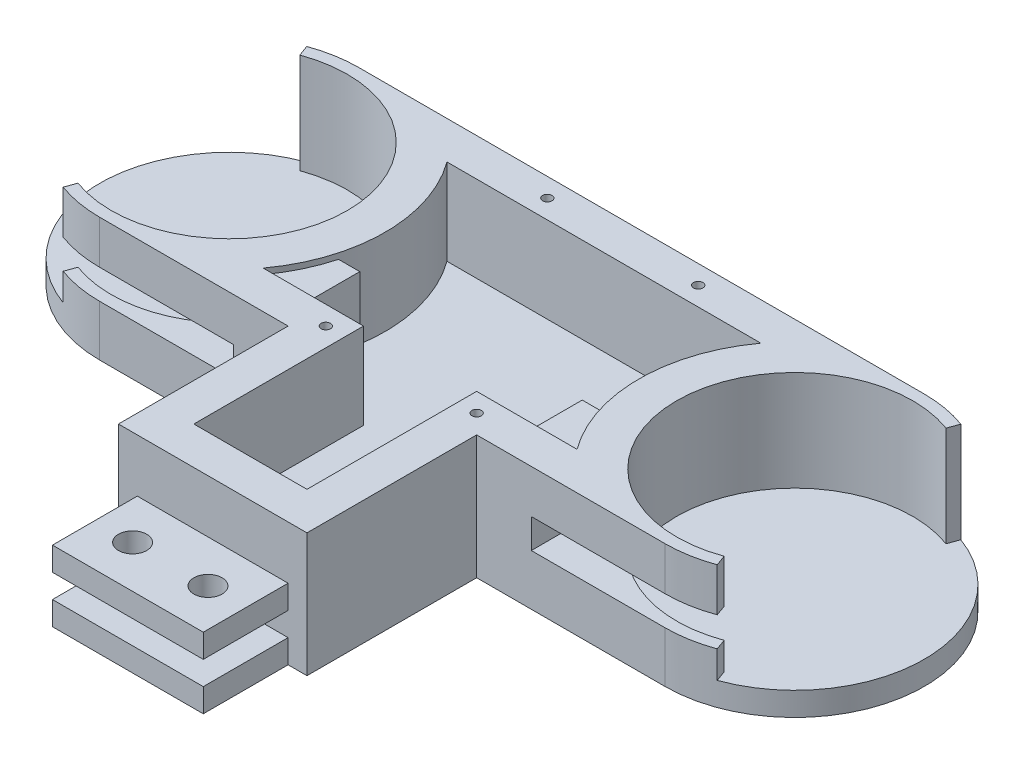
SolidWorks part; units mm, degrees
material "ABS PC"
ref_plane "Front Plane" through (0, 0, 0) normal (0, 0, 1) x (1, 0, 0)
ref_plane "Top Plane" through (0, 0, 0) normal (0, 1, 0) x (1, 0, 0)
ref_plane "Right Plane" through (0, 0, 0) normal (1, 0, 0) x (0, 0, -1)
sketch "Sketch1" plane through (0, 0, 0) normal (0, 1, 0) x (1, 0, 0)
  line L0 (-62.5313, 48.6245) -> (13.6438, 48.6245)
  line L1 (13.6438, 48.6245) -> (13.6438, -21.2255)
  line L2 (13.6438, -21.2255) -> (-62.5313, -21.2255)
  line L3 (-62.5313, 13.6995) -> (-74.4763, 46.5183)
  line L4 (-62.5313, 13.6995) -> (-74.4763, -19.1192)
  line L5 (-62.5313, 48.6245) -> (-62.5313, -21.2255)
  circle A0 centre (-62.5313, 13.6995) radius 34.925
  circle A1 centre (-62.5313, 13.6995) radius 31.8135
  dimension "D3" = 63.627
  dimension "D4" = 69.85
  dimension "D1" = 20
  dimension "D2" = 20
extrude "Boss-Extrude1" add sketch "Sketch1" along normal blind 26.9875 contours A1 L5 A0 | A1 L5 A0 L3 | A1 L4 A0 L5 | A0 L2 L1 L0 region at (-38.3878, 0, -37.843) region at (-11.352, 0, -13.6995) region at (-68.3006, 0, -46.4189) region at (-68.3006, 0, 19.0199)
extrude "Boss-Extrude5" add sketch "Sketch1<5>" against normal blind 6.35 contours A0 L2 L1 L0 | A0 region at (-11.352, 0, -13.6995)
sketch "Sketch1<5>" plane through (0, 0, 0) normal (0, 1, 0) x (1, 0, 0) same geometry as "Sketch1"
sketch "Sketch2" plane through (0, 26.9875, 0) normal (0, 1, 0) x (1, 0, 0)
  line L0 (-62.5313, 13.6995) -> (-53.4175, 13.6995)
  line L1 (-53.4175, 13.6995) -> (-53.4175, 3.6695)
  line L2 (13.6438, -21.2255) -> (-62.5313, -21.2255) construction
  line L3 (-53.4175, 3.6695) -> (-32.4413, 3.6695)
  line L4 (-53.4175, 3.6695) -> (-53.4175, 23.7295)
  line L5 (-53.4175, 23.7295) -> (-32.4413, 23.7295)
  line L6 (-32.4413, 3.6695) -> (-32.4413, 23.7295)
  line L7 (-53.4175, 3.6695) -> (-53.4175, -21.2255)
  line L8 (-53.4175, -21.2255) -> (13.6438, -21.2255)
  line L9 (13.6438, -21.2255) -> (13.6438, 48.6245)
  line L10 (13.6438, 48.6245) -> (-53.4175, 48.6245)
  line L11 (-62.5313, 48.6245) -> (13.6438, 48.6245) construction
  line L12 (-53.4175, 48.6245) -> (-53.4175, 23.7295)
  dimension "D1" = 9.1137
  dimension "D2" = 20.9763
  dimension "D3" = 20.06
  dimension "D4" = 10.03
mirror "Mirror1" about plane through (13.6438, 26.9875, 0) normal (1, 0, 0) of "Boss-Extrude1", "Boss-Extrude5"
sketch "Sketch3" plane through (0, 0, 21.2255) normal (0, 0, 1) x (1, 0, 0)
  line L0 (-53.4175, 26.9875) -> (13.6438, 26.9875) construction
  line L1 (-11.7562, 26.9875) -> (39.0438, 26.9875)
  line L2 (-11.7562, 26.9875) -> (-11.7562, -6.35)
  line L3 (-11.7562, -6.35) -> (39.0438, -6.35)
  line L4 (39.0438, 26.9875) -> (39.0438, -6.35)
  line L5 (89.8188, -6.35) -> (-62.5313, -6.35) construction
  line L8 (13.6438, 26.9875) -> (13.6438, -6.35)
  line L9 (89.8188, 26.9875) -> (-62.5313, 26.9875) construction
  line M5 (-62.5313, -6.35) -> (89.8188, -6.35)
  line M7 (89.8188, 26.9875) -> (-62.5313, 26.9875)
  dimension "D1" = 50.8
  dimension "D2" = 25.4
extrude "Boss-Extrude7" add sketch "Sketch3" along normal blind 45.72 contours L8 L1 L2 M5 | L8 L3 L4 M7 region at (0.9438, 10.3187, 21.2255) region at (26.3438, 10.3187, 21.2255)
sketch "Sketch6" plane through (0, 0, 66.9455) normal (0, 0, 1) x (1, 0, 0)
  line L0 (39.0438, 26.9875) -> (-11.7562, 26.9875) construction
  line L1 (4.7538, 26.9875) -> (22.5338, 26.9875)
  line L2 (4.7538, 26.9875) -> (4.7538, -6.35)
  line L3 (4.7538, -6.35) -> (22.5338, -6.35)
  line L4 (22.5338, 26.9875) -> (22.5338, -6.35)
  line L5 (-11.7562, -6.35) -> (39.0438, -6.35) construction
  line L6 (13.6438, 26.9875) -> (13.6438, -6.35)
  line M4 (-11.7562, -6.35) -> (39.0438, -6.35)
  line M6 (39.0438, 26.9875) -> (-11.7562, 26.9875)
  dimension "D1" = 17.78
  dimension "D2" = 8.89
extrude "Boss-Extrude8" add sketch "Sketch6" along normal blind 22.86 contours L6 L1 L2 M4 | L6 L3 L4 M6 region at (9.1988, 10.3188, 66.9455) region at (18.0888, 10.3187, 66.9455)
sketch "Sketch7" plane through (4.7538, 0, 0) normal (-1, 0, 0) x (0, 0, 1)
  line L0 (89.8055, 26.9875) -> (89.8055, -6.35) construction
  line L1 (66.9455, 26.9875) -> (89.8055, 26.9875)
  line L2 (66.9455, 26.9875) -> (66.9455, 12.446)
  line L3 (66.9455, 12.446) -> (89.8055, 12.446)
  line L4 (89.8055, 26.9875) -> (89.8055, 12.446)
  line L5 (66.9455, 26.9875) -> (66.9455, -6.35) construction
  line L6 (66.9455, 6.35) -> (89.8055, 6.35)
  line L7 (66.9455, 6.35) -> (66.9455, -0.254)
  line L8 (66.9455, -0.254) -> (89.8055, -0.254)
  line L9 (89.8055, 6.35) -> (89.8055, -0.254)
  line L10 (89.8055, -6.35) -> (66.9455, -6.35) construction
  dimension "D1" = 6.096
  dimension "D2" = 6.604
  dimension "D3" = 6.096
extrude "Cut-Extrude1" cut sketch "Sketch7" against normal blind 21.082
sketch "Sketch11" plane through (0, 0, 21.2255) normal (0, 0, 1) x (1, 0, 0)
  line L1 (-77.744, 15.3035) -> (-26.4882, 15.3035)
  line L2 (-77.744, 15.3035) -> (-77.744, 7.366)
  line L3 (-77.744, 7.366) -> (-26.4882, 7.366)
  line L4 (-26.4882, 15.3035) -> (-26.4882, 7.366)
  line L5 (-11.7562, 26.9875) -> (-62.5313, 26.9875) construction
  line L7 (-11.7562, -6.35) -> (-62.5313, -6.35) construction
  line L8 (-11.7562, 26.9875) -> (-11.7562, -6.35) construction
  dimension "D1" = 11.684
  dimension "D2" = 13.716
  dimension "D3" = 14.732
extrude "Cut-Extrude3" cut sketch "Sketch11" against normal blind 13.716
sketch "Sketch12" plane through (0, 26.9875, 0) normal (0, 1, 0) x (1, 0, 0)
  line L0 (13.6438, -66.9455) -> (13.6438, 48.6245)
  line L1 (39.0438, -66.9455) -> (-11.7562, -66.9455) construction
  line L2 (-62.5313, 48.6245) -> (89.8188, 48.6245) construction
ref_plane "Plane1" through (13.6438, 0, 0) normal (1, 0, 0) x (0, 0, -1)
mirror "Mirror2" about plane through (13.6438, 0, 0) normal (1, 0, 0) of "Cut-Extrude3"
shell "Shell1" thickness 10.16 removed face at (13.6438, 26.9875, 0.7467)
sketch "Sketch13" plane through (0, 26.9875, 0) normal (0, 1, 0) x (1, 0, 0)
  circle A0 centre (33.9638, -16.1455) radius 1.2687
  circle A1 centre (-6.6762, -16.1455) radius 1.2687
  circle A2 centre (-6.6762, 43.5445) radius 1.2687
  circle A3 centre (33.9638, 43.5445) radius 1.2687
  dimension "D1" = 2.5375
  dimension "D2" = 2.5375
  dimension "D3" = 2.5375
  dimension "D4" = 2.5375
extrude "Cut-Extrude4" cut sketch "Sketch13" against normal blind 35.56
sketch "Sketch14" plane through (0, 0, 66.9455) normal (0, 0, 1) x (1, 0, 0)
  line L0 (-11.7562, -6.35) -> (4.7538, -6.35) construction
  line L1 (-6.6762, 6.35) -> (33.9638, 6.35)
  line L2 (-6.6762, 6.35) -> (-6.6762, 12.7)
  line L3 (-6.6762, 12.7) -> (33.9638, 12.7)
  line L4 (33.9638, 6.35) -> (33.9638, 12.7)
  line L5 (-6.6762, -6.35) -> (33.9638, -6.35)
  line L6 (-6.6762, -6.35) -> (-6.6762, 0)
  line L7 (-6.6762, 0) -> (33.9638, 0)
  line L8 (33.9638, -6.35) -> (33.9638, 0)
  line L9 (13.6438, -18.3356) -> (13.6438, 18.3356) construction
  dimension "D1" = 20.32
  dimension "D2" = 20.32
  dimension "D3" = 6.35
  dimension "D4" = 6.35
  dimension "D5" = 20.32
  dimension "D6" = 20.32
  dimension "D7" = 6.35
extrude "Boss-Extrude9" add sketch "Sketch14" along normal up to surface (22.86 mm away) up to face at (13.6438, -3.302, 89.8055)
sketch "Sketch16" plane through (0, 12.7, 0) normal (0, 1, 0) x (1, 0, 0)
  line L0 (13.6438, -18.3356) -> (13.6438, 18.3356) construction
  line L1 (33.9638, -89.8055) -> (-6.6762, -89.8055) construction
  circle A0 centre (3.4838, -78.3755) radius 8.89 construction
  circle A1 centre (3.4838, -78.3755) radius 3.81
  dimension "D1" = 17.78
  dimension "D4" = 7.62
  dimension "D2" = 10.16
  dimension "D3" = 11.43
extrude "Cut-Extrude5" cut sketch "Sketch16" against normal up to surface (19.05 mm away) up to face at (13.6438, -6.35, 36.2538)
mirror "Mirror3" about plane through (13.6438, 0, 0) normal (1, 0, 0) of "Cut-Extrude5"
